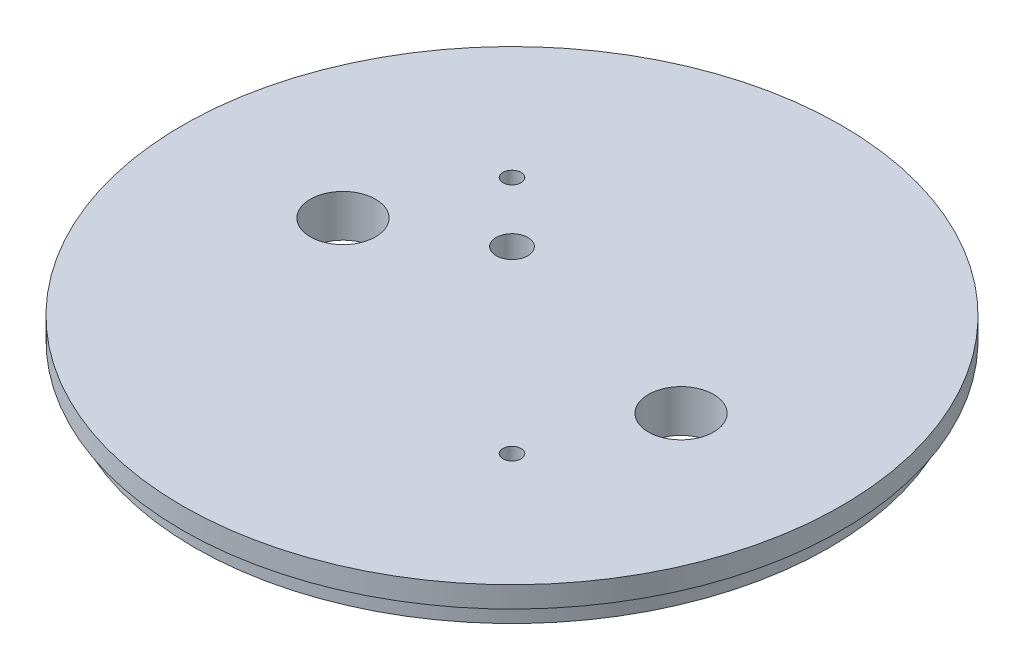
SolidWorks part; units mm, degrees
material "6061-T4 (SS)"
ref_plane "Front Plane" through (0, 0, 0) normal (0, 0, 1) x (1, 0, 0)
ref_plane "Top Plane" through (0, 0, 0) normal (0, 1, 0) x (1, 0, 0)
ref_plane "Right Plane" through (0, 0, 0) normal (1, 0, 0) x (0, 0, -1)
sketch "Sketch1" plane through (0, 0, 0) normal (0, 1, 0) x (1, 0, 0)
  line L0 (0, -49.5173) -> (0, 49.5173) construction
  line L1 (-49.5173, 0) -> (49.5173, 0) construction
  line L2 (-17.9605, 17.9605) -> (0, 0) construction
  line L3 (0, 56.7387) -> (0, 29.6936) construction
  line L4 (3.6407, 56.7387) -> (3.6407, 29.6936) construction
  line L5 (-3.6407, 56.7387) -> (-3.6407, 29.6936) construction
  line L6 (0, -56.7387) -> (0, -29.6936) construction
  line L7 (3.6407, -56.7387) -> (3.6407, -29.6936) construction
  line L8 (-3.6407, -56.7387) -> (-3.6407, -29.6936) construction
  line L9 (-35.014, -35.014) -> (54.3236, 54.3236) construction
  circle A0 centre (0, 0) radius 49.5173
  circle A1 centre (0, 0) radius 3.175 construction
  circle A2 centre (25.4, 0) radius 4.9022
  circle A3 centre (-25.4, 0) radius 4.9022
  circle A4 centre (-17.9605, 17.9605) radius 1.3589
  arc A6 (3.6407, 56.7387) -> (-3.6407, 56.7387) centre (0, 56.7387) ccw construction
  arc A7 (-3.6407, 29.6936) -> (3.6407, 29.6936) centre (0, 29.6936) ccw construction
  arc A8 (3.6407, -56.7387) -> (-3.6407, -56.7387) centre (0, -56.7387) cw construction
  arc A9 (-3.6407, -29.6936) -> (3.6407, -29.6936) centre (0, -29.6936) cw construction
  circle A10 centre (17.9605, -17.9605) radius 1.3589
  circle A11 centre (-8.9803, 8.9803) radius 2.3813
  circle A12 centre (8.9803, -8.9803) radius 2.3813 construction
  point P16 (0, 43.2162)
  point P19 (0, 0)
  point P26 (0, -43.2162)
  dimension "D1" = 99.0346
  dimension "D2" = 6.35
  dimension "D3" = 9.8044
  dimension "D5" = 2.7178
  dimension "D8" = 4.7625
  dimension "D6" = 25.4
  dimension "D7" = 45
  dimension "D4" = 45
  dimension "D9" = 25.4
extrude "Boss-Extrude1" add sketch "Sketch1" along normal blind 6.35
sketch "Sketch2" plane through (0, 0, 0) normal (0, -1, 0) x (1, 0, 0)
  circle A0 centre (0, 0) radius 49.5173
  circle A1 centre (0, 0) radius 47.6885
  dimension "D1" = 99.0346
  dimension "D2" = 95.377
extrude "Cut-Extrude1" cut sketch "Sketch2" against normal blind 3.175
sketch "Sketch3" plane through (0, 6.35, 0) normal (0, 1, 0) x (1, 0, 0)
  line L0 (0, 49.5173) -> (0, -49.5173) construction
  line L1 (-49.5173, 0) -> (49.5173, 0) construction
  line L2 (0, 34.925) -> (0, 13.335) construction
  line L3 (3.2385, 34.925) -> (3.2385, 13.335)
  line L4 (-3.2385, 34.925) -> (-3.2385, 13.335)
  line L5 (0, -34.925) -> (0, -13.335) construction
  line L6 (3.2385, -34.925) -> (3.2385, -13.335)
  line L7 (-3.2385, -34.925) -> (-3.2385, -13.335)
  circle A0 centre (0, 0) radius 49.5173 construction
  arc A1 (3.2385, 34.925) -> (-3.2385, 34.925) centre (0, 34.925) ccw
  arc A2 (-3.2385, 13.335) -> (3.2385, 13.335) centre (0, 13.335) ccw
  arc A3 (3.2385, -34.925) -> (-3.2385, -34.925) centre (0, -34.925) cw
  arc A4 (-3.2385, -13.335) -> (3.2385, -13.335) centre (0, -13.335) cw
  point P7 (0, 13.335)
  point P8 (0, 34.925)
  point P12 (0, 24.13)
  point P20 (0, -24.13)
  point P25 (0, -34.925)
  point P26 (0, -13.335)
  dimension "D1" = 13.335
  dimension "D2" = 34.925
  dimension "D3" = 6.477
extrude "Cut-Extrude2" cut sketch "Sketch3" against normal blind 3.81 from offset 2.794 offset against normal yes
equation "\"Coupler_OD\" = 3.899in"
equation "\"Coupler_ID\" = 3.755in"
equation "\"Lead_Screw_Hole_Diam\" = 0.386in"
equation "\"Lead_Screw_Dist\" = 2in"
equation "\"D9@Sketch1\"=\"Lead_Screw_Dist\"/2"
equation "\"D3@Sketch1\"= \"Lead_Screw_Hole_Diam\""
equation "\"Body_Tube_OD\"= 4.024in"
equation "\"Body_Tube_ID\"= 3.90in"
equation "\"Avionics_Bulkhead_Thickness\" = 0.25in"
equation "\"Avionics_Bulkhead_Lip\" = 0.125in"
equation "\"Lead_Screw_Diam\" = 0.375in"
equation "\"D1@Sketch2\"=\"Coupler_OD\""
equation "\"D2@Sketch2\"=\"Coupler_ID\""
equation "\"D1@Sketch1\"=\"Coupler_OD\""
equation "\"D1@Boss-Extrude1\"=\"Avionics_Bulkhead_Thickness\""
equation "\"D1@Cut-Extrude1\"=\"Avionics_Bulkhead_Lip\""
